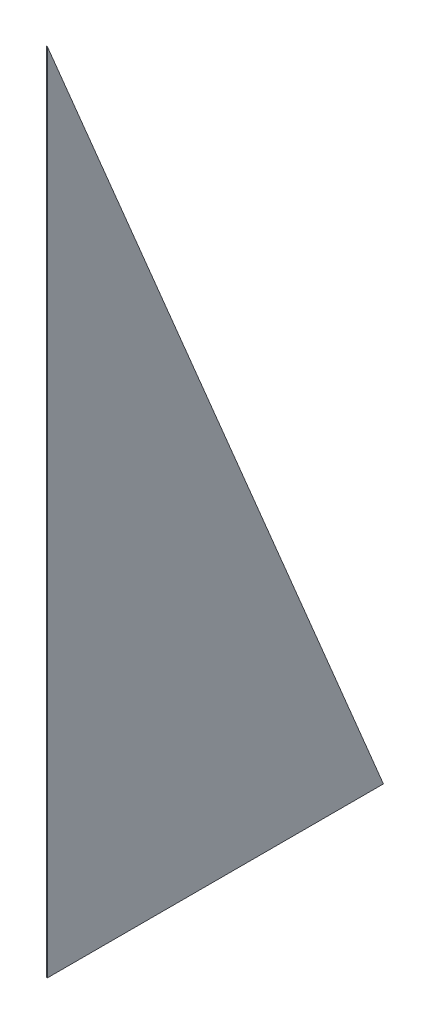
SolidWorks part; units mm, degrees
ref_plane "Front Plane" through (0, 0, 0) normal (0, 0, 1) x (1, 0, 0)
ref_plane "Top Plane" through (0, 0, 0) normal (0, 1, 0) x (1, 0, 0)
ref_plane "Right Plane" through (0, 0, 0) normal (1, 0, 0) x (0, 0, -1)
sketch "Sketch1" plane through (0, 0, 0) normal (1, 0, 0) x (0, 0, -1)
  line L0 (0, 0) -> (0, 1200)
  line L1 (0, 1200) -> (500, 0)
  line L2 (500, 0) -> (0, 0)
  dimension "D1" = 1200
  dimension "D2" = 500
extrude "Boss-Extrude1" add sketch "Sketch1" along normal blind 1
